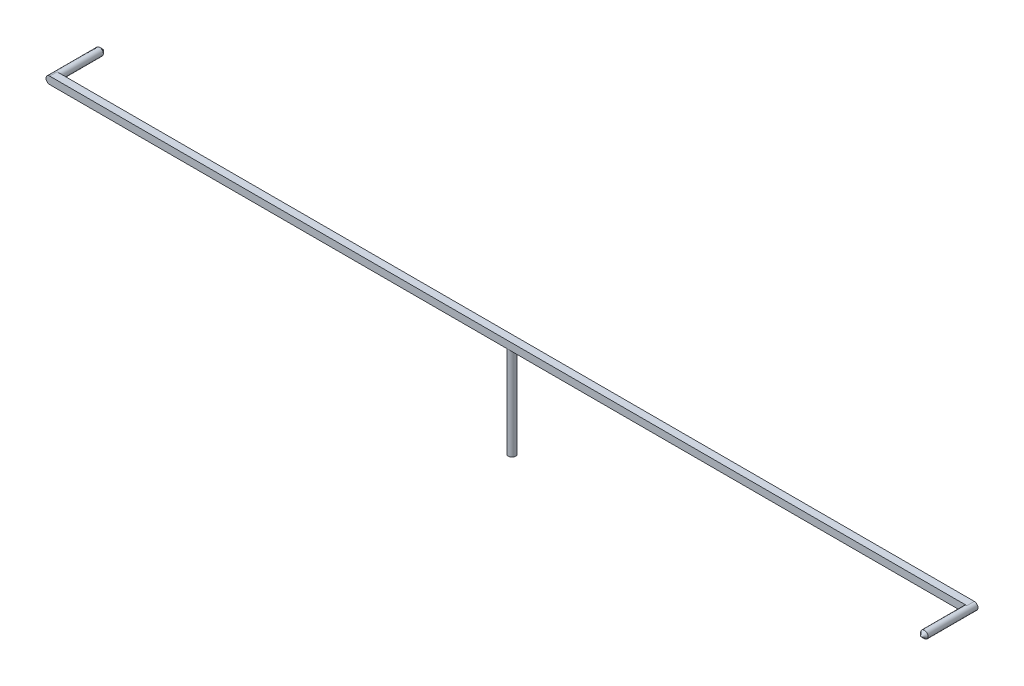
SolidWorks part; units mm, degrees
ref_plane "前视基准面" through (0, 0, 0) normal (0, 0, 1) x (1, 0, 0)
ref_plane "上视基准面" through (0, 0, 0) normal (0, 1, 0) x (1, 0, 0)
ref_plane "右视基准面" through (0, 0, 0) normal (1, 0, 0) x (0, 0, -1)
sketch "草图1" plane through (0, 0, 0) normal (0, 1, 0) x (1, 0, 0)
  circle A0 centre (0, 0) radius 0.4
  dimension "D1" = 0.8
extrude "凸台-拉伸1" add sketch "草图1" along normal blind 10
sketch "草图2" plane through (0, 10, 0) normal (0, 1, 0) x (1, 0, 0)
  line L1 (-50, 0.4) -> (50, 0.4)
  line L2 (-50, 0.4) -> (-50, -0.4)
  line L3 (-50, -0.4) -> (50, -0.4)
  line L4 (50, 0.4) -> (50, -0.4)
  circle A0 centre (0, 0) radius 0.4 construction
  dimension "D1" = 50
  dimension "D2" = 50
extrude "凸台-拉伸2" add sketch "草图2" along normal blind 0.8
fillet "圆角1" radius 0.4 4 edges at (50, 10, 0) (50, 10.8, 0) (-50, 10, 0) (-50, 10.8, 0)
sketch "草图3" plane through (0, 0, 0.4) normal (0, 0, 1) x (1, 0, 0)
  circle A0 centre (49.6, 10.4) radius 0.4
  dimension "D1" = 0.8
extrude "凸台-拉伸3" add sketch "草图3" along normal blind 5
sketch "草图4" plane through (0, 0, -0.4) normal (0, 0, -1) x (-1, 0, 0)
  circle A0 centre (49.6, 10.4) radius 0.4
  dimension "D1" = 0.8
extrude "凸台-拉伸4" add sketch "草图4" along normal blind 5
chamfer "倒角1" distance 0.4 angle 45 2 edges at (-50, 10.4, -5.4) (50, 10.4, 5.4)
